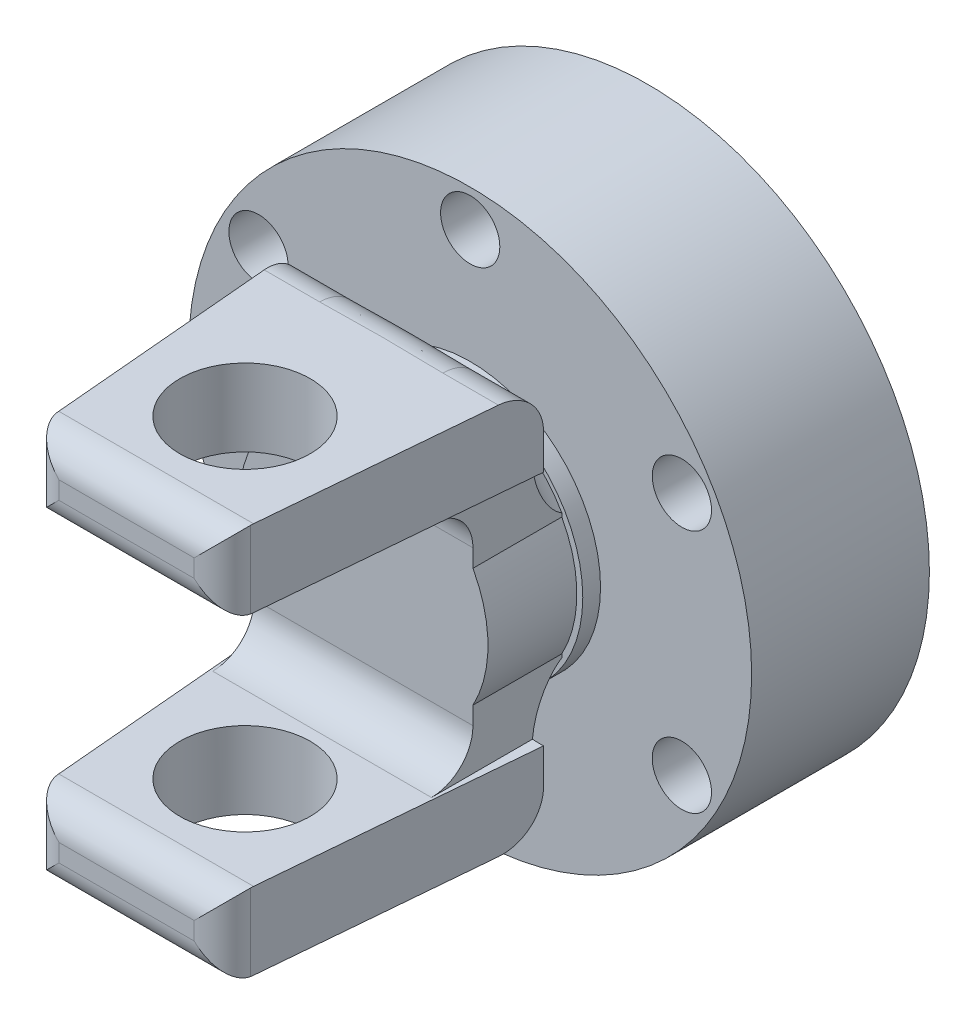
SolidWorks part; units mm, degrees
ref_plane "Płaszczyzna przednia" through (0, 0, 0) normal (0, 0, 1) x (1, 0, 0)
ref_plane "Płaszczyzna górna" through (0, 0, 0) normal (0, 1, 0) x (1, 0, 0)
ref_plane "Płaszczyzna prawa" through (0, 0, 0) normal (1, 0, 0) x (0, 0, -1)
sketch "Szkic1" plane through (0, 0, 0) normal (0, 0, 1) x (1, 0, 0)
  circle A0 centre (0, 0) radius 47.5
  dimension "D1" = 95
extrude "Dodanie-wyciągnięcie1" add sketch "Szkic1" along normal blind 30 contours A0
sketch "Szkic2" plane through (0, 0, 30) normal (0, 0, 1) x (1, 0, 0)
  circle A0 centre (0, 41.25) radius 5
  dimension "D1" = 10
  dimension "D2" = 41.25
extrude "Wytnij-wyciągnięcie1" cut sketch "Szkic2" against normal up to next
pattern_circular "Szyk kołowy1" count 6 over 360 about axis through (0, 0, 30) along (0, 0, 1) of "Wytnij-wyciągnięcie1"
sketch "Szkic3" plane through (0, 0, 30) normal (0, 0, 1) x (1, 0, 0)
  circle A0 centre (0, 0) radius 21
  dimension "D1" = 42
extrude "Dodanie-wyciągnięcie2" add sketch "Szkic3" along normal blind 0.001
sketch "Szkic5" plane through (0, 0, 30.001) normal (0, 0, 1) x (1, 0, 0)
  circle A0 centre (0, 0) radius 22
  dimension "D1" = 44
extrude "Dodanie-wyciągnięcie4" add sketch "Szkic5" along normal blind 3
sketch "Szkic7" plane through (0, 0, 33.001) normal (0, 0, 1) x (1, 0, 0)
  circle A0 centre (0, 0) radius 21 construction
  circle A1 centre (0, 0) radius 21
extrude "Dodanie-wyciągnięcie5" add sketch "Szkic7" along normal blind 15
ref_plane "Płaszczyzna2" through (0, 26.5, 0) normal (0, 1, 0) x (1, 0, 0)
sketch "Szkic9" plane through (0, 26.5, 0) normal (0, 1, 0) x (1, 0, 0)
  line L0 (-20.3744, -38.001) -> (-16, -88.001)
  line L1 (-16, -88.001) -> (16, -88.001)
  line L2 (16, -88.001) -> (20.3744, -38.001)
  line L3 (20.3744, -38.001) -> (-20.3744, -38.001)
  line L4 (-21, -48.001) -> (21, -48.001) construction
  point P7 (0, -88.001)
  dimension "D1" = 50
  dimension "D2" = 32
  dimension "D3" = 95
  dimension "D4" = 95
  dimension "D5" = 10
extrude "Dodanie-wyciągnięcie6" add sketch "Szkic9" along normal mid plane 13 contours L1 L2 L3 L0
ref_plane "Płaszczyzna3" through (0, 10, 0) normal (0, 1, 0) x (1, 0, 0)
sketch "Szkic14" plane through (0, 10, 0) normal (0, 1, 0) x (1, 0, 0)
  line L1 (-18.4662, -38.001) -> (18.4662, -38.001)
  line L2 (-18.4662, -38.001) -> (-18.4662, -48.001)
  line L3 (-18.4662, -48.001) -> (18.4662, -48.001)
  line L4 (18.4662, -38.001) -> (18.4662, -48.001)
  dimension "D1" = 10
extrude "Dodanie-wyciągnięcie7" add sketch "Szkic14" along normal up to next (23 mm away)
fillet "Zaokrąglenie1" radius 7 2 edges at (0, 21, 38.001) (0, 20, 48.001)
fillet "Zaokrąglenie2" radius 7 1 edges at (0, 33, 38.001)
fillet "Zaokrąglenie3" radius 5 4 edges at (-16, 26.5, 88.001) (0, 33, 88.001) (16, 26.5, 88.001) (0, 20, 88.001)
sketch "Szkic16" plane through (0, 33, 0) normal (0, 1, 0) x (1, 0, 0)
  line L0 (11.4183, -88.001) -> (-11.4183, -88.001) construction
  circle A0 centre (0, -68.001) radius 11
  dimension "D1" = 22
  dimension "D2" = 20
extrude "Wytnij-wyciągnięcie2" cut sketch "Szkic16" against normal up to next contours A0
mirror "Lustro1" about plane through (0, 0, 0) normal (0, 1, 0) of "Dodanie-wyciągnięcie7", "Zaokrąglenie1", "Zaokrąglenie2", "Zaokrąglenie3", "Dodanie-wyciągnięcie6", "Wytnij-wyciągnięcie2"
